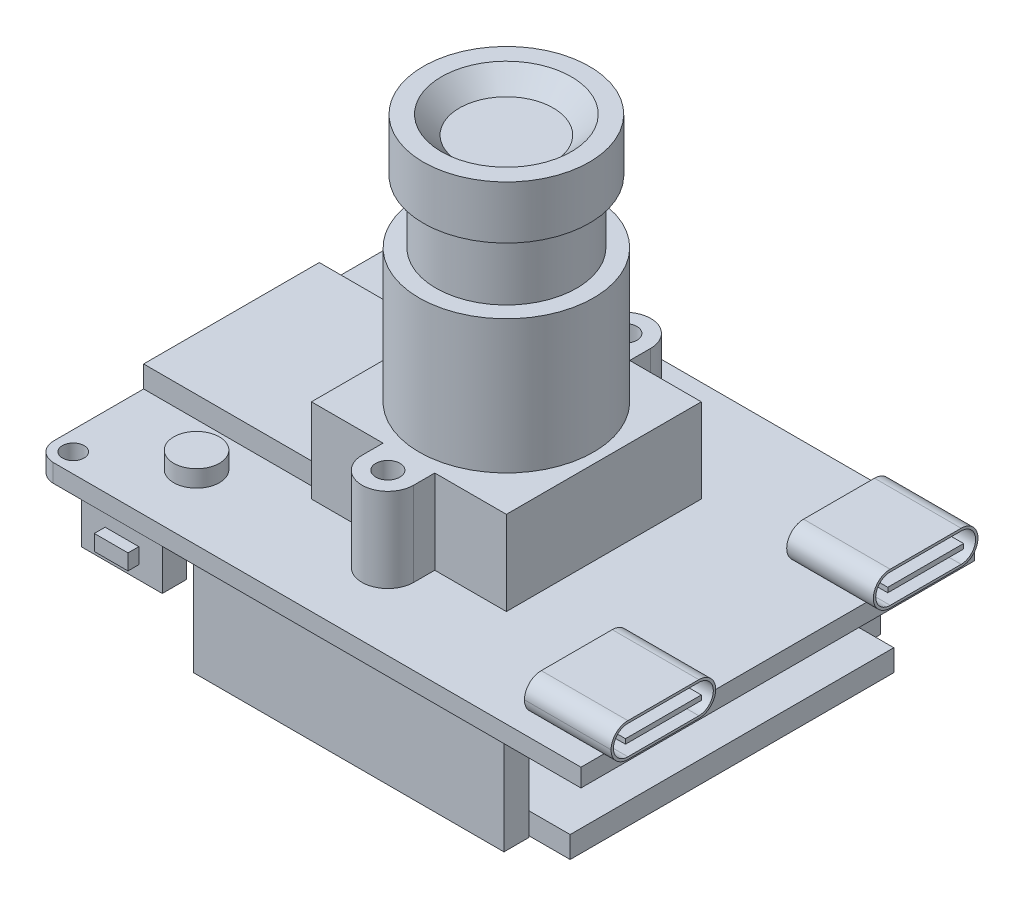
SolidWorks part; units mm, degrees
ref_plane "Alzado" through (0, 0, 0) normal (0, 0, 1) x (1, 0, 0)
ref_plane "Planta" through (0, 0, 0) normal (0, 1, 0) x (1, 0, 0)
ref_plane "Vista lateral" through (0, 0, 0) normal (1, 0, 0) x (0, 0, -1)
sketch "Croquis2" plane through (0, 0, 0) normal (0, 1, 0) x (1, 0, 0)
  line L1 (-16.6358, 13.4216) -> (28.7642, 13.4216)
  line L2 (-16.6358, 13.4216) -> (-16.6358, -19.2784)
  line L3 (-16.6358, -19.2784) -> (28.7642, -19.2784)
  line L4 (28.7642, 13.4216) -> (28.7642, -19.2784)
  dimension "D1" = 45.4
  dimension "D2" = 32.7
extrude "Saliente-Extruir1" add sketch "Croquis2" along normal blind 1.5
sketch "Croquis4" plane through (0, 1.5, 0) normal (0, 1, 0) x (1, 0, 0)
  line L0 (28.7642, -19.2784) -> (28.7642, 13.4216) construction
  line L1 (-1.7358, 5.0216) -> (4.2137, 5.0216)
  line L2 (-1.7358, 5.0216) -> (-1.7358, -11.1784)
  line L3 (-1.7358, -11.1784) -> (4.2137, -11.1784)
  line L4 (14.4642, 5.0216) -> (14.4642, -11.1784)
  line L5 (28.7642, 13.4216) -> (-16.6358, 13.4216) construction
  line L6 (6.3637, -12.9284) -> (6.3637, 6.7716) construction
  line L7 (6.3637, 6.7716) -> (6.3637, 8.9216) construction
  line L8 (-1.7358, -3.0784) -> (14.4642, -3.0784) construction
  line L9 (8.5137, 5.0216) -> (14.4642, 5.0216)
  line L11 (4.2137, 5.0216) -> (4.2137, 6.7716)
  line L13 (8.5137, 5.0216) -> (8.5137, 6.7716)
  line L14 (6.3637, -12.9284) -> (6.3637, -15.0784) construction
  line L15 (6.3637, 6.7716) -> (6.3637, -12.9284) construction
  line L16 (8.5137, -11.1784) -> (8.5137, -12.9284)
  line L17 (4.2137, -11.1784) -> (4.2137, -12.9284)
  line L18 (8.5137, -11.1784) -> (14.4642, -11.1784)
  line L19 (-1.7358, -11.1784) -> (4.2137, -11.1784)
  line L20 (8.5137, -11.1784) -> (14.4642, -11.1784)
  arc A0 (4.2137, 6.7716) -> (8.5137, 6.7716) centre (6.3637, 6.7716) cw
  arc A1 (4.2137, -12.9284) -> (8.5137, -12.9284) centre (6.3637, -12.9284) ccw
  circle A2 centre (6.3637, 6.7716) radius 1
  circle A3 centre (6.3637, -12.9284) radius 1
  point P18 (6.3637, 8.9216)
  dimension "D6" = 4.3
  dimension "D9" = 2
  dimension "D1" = 16.2
  dimension "D2" = 16.2
  dimension "D3" = 14.3
  dimension "D4" = 8.4
  dimension "D5" = 24
  dimension "D7" = 3.9
  dimension "D8" = 8.0995
extrude "Saliente-Extruir3" add sketch "Croquis4" along normal blind 7 contours L17 A1 L16 L18 L4 L9 L13 A0 L11 L1 L2 L3
sketch "Croquis5" plane through (0, 8.5, 0) normal (0, 1, 0) x (1, 0, 0)
  line L0 (-1.7358, -3.0784) -> (14.4642, -3.0784) construction
  line L1 (-1.7358, 5.0216) -> (-1.7358, -11.1784) construction
  line L2 (14.4642, 5.0216) -> (14.4642, -11.1784) construction
  circle A0 centre (6.3642, -3.0784) radius 7.25
  point P6 (6.3642, -3.0784)
  dimension "D1" = 14.5
extrude "Saliente-Extruir4" add sketch "Croquis5" along normal blind 11.1
sketch "Croquis7" plane through (0, 19.6, 0) normal (0, 1, 0) x (1, 0, 0)
  line L0 (-0.8858, -3.0784) -> (13.6142, -3.0784) construction
  circle A0 centre (6.3642, -3.0784) radius 7.25 construction
  circle A1 centre (6.3642, -3.0784) radius 7.25 construction
  circle A2 centre (6.3642, -3.0784) radius 5.85
  dimension "D1" = 11.7
extrude "Saliente-Extruir5" add sketch "Croquis7" along normal blind 5.2
sketch "Croquis13" plane through (0, 1.5, 0) normal (0, 1, 0) x (1, 0, 0)
  line L0 (28.7642, 13.4216) -> (-16.6358, 13.4216) construction
  line L1 (22.9642, 12.3216) -> (30.1642, 12.3216)
  line L2 (22.9642, 12.3216) -> (22.9642, 3.6216)
  line L3 (22.9642, 3.6216) -> (30.1642, 3.6216)
  line L4 (30.1642, 12.3216) -> (30.1642, 3.6216)
  line L5 (28.7642, -19.2784) -> (28.7642, 13.4216) construction
  line L6 (-16.6358, -2.9284) -> (28.7642, -2.9284) construction
  line L7 (-16.6358, 13.4216) -> (-16.6358, -19.2784) construction
  line L8 (30.1642, -18.1784) -> (30.1642, -9.4784)
  line L9 (22.9642, -9.4784) -> (30.1642, -9.4784)
  line L10 (22.9642, -18.1784) -> (22.9642, -9.4784)
  line L11 (22.9642, -18.1784) -> (30.1642, -18.1784)
  dimension "D1" = 8.7
  dimension "D2" = 7.2
  dimension "D3" = 1.1
  dimension "D4" = 1.4
extrude "Saliente-Extruir16" add sketch "Croquis13" along normal blind 2.8 contours L9 L8 L11 L10
sketch "Croquis20" plane through (30.1642, 0, 0) normal (1, 0, 0) x (0, 0, -1)
  line L0 (-16.7784, 2.9) -> (-10.8784, 2.9) construction
  line L1 (-16.7784, 4.3) -> (-10.8784, 4.3)
  line L2 (-16.7784, 1.5) -> (-10.8784, 1.5)
  line L3 (-18.1784, 1.5) -> (-9.4784, 1.5) construction
  line L4 (-9.4784, 4.3) -> (-9.4784, 1.5) construction
  line L5 (-18.1784, 4.3) -> (-18.1784, 1.5)
  line L6 (-18.1784, 1.5) -> (-16.7784, 1.5)
  line L7 (-10.8784, 4.3) -> (-9.4784, 4.3)
  line L8 (-9.4784, 4.3) -> (-9.4784, 1.5)
  line L9 (-9.4784, 1.5) -> (-10.8784, 1.5)
  arc A0 (-16.7784, 4.3) -> (-16.7784, 1.5) centre (-16.7784, 2.9) ccw
  arc A1 (-10.8784, 1.5) -> (-10.8784, 4.3) centre (-10.8784, 2.9) ccw
  arc A2 (-16.7784, 4.3) -> (-16.7502, 1.5) centre (-16.7782, 2.8999) ccw
  arc A3 (-10.8784, 4.3) -> (-10.8784, 1.5) centre (-10.8784, 2.9) cw
  spline S0 degree 1 poles (-16.7784, 4.3) (-18.1784, 4.3) knots 0 0 1 1
  point P2 (-13.8284, 2.9)
  point P7 (-18.1784, 2.9)
  point P8 (-9.4784, 2.9)
  line M5 (-18.1784, 1.5) -> (-9.4784, 1.5)
  line M6 (-9.4784, 1.5) -> (-9.4784, 4.3)
  line M7 (-9.4784, 4.3) -> (-18.1784, 4.3)
  line M8 (-18.1784, 4.3) -> (-18.1784, 1.5)
  dimension "D1" = 8.7
  dimension "D2" = 2.8
extrude "Cortar-Extruir2" cut sketch "Croquis20" against normal blind 7.2 contours A0 M7 M8 | A2 L5 M5 | A1 L8 M7 | A1 M5 M6
sketch "Croquis28" plane through (30.1642, 0, 0) normal (1, 0, 0) x (0, 0, -1)
  line L0 (-16.7784, 2.9) -> (-10.8784, 2.9) construction
  line L1 (-16.7784, 4.1) -> (-10.8784, 4.1)
  line L2 (-16.7784, 1.7) -> (-10.8784, 1.7)
  line L3 (-16.7784, 4.3) -> (-10.8784, 4.3) construction
  line L4 (-16.8063, 1.5) -> (-10.8784, 1.5) construction
  arc A0 (-16.7784, 4.1) -> (-16.7784, 1.7) centre (-16.7784, 2.9) ccw
  arc A1 (-10.8784, 1.7) -> (-10.8784, 4.1) centre (-10.8784, 2.9) ccw
  arc A2 (-10.8784, 1.5) -> (-10.8784, 4.3) centre (-10.8784, 2.9) ccw construction
  point P2 (-13.8284, 2.9)
  point P7 (-9.6784, 2.9)
  point P11 (-9.4784, 2.9)
  point P12 (-17.9784, 2.9)
  dimension "D1" = 0.2
  dimension "D2" = 0.2
  dimension "D3" = 0.2
  dimension "D4" = 0.2
sketch "Croquis29" plane through (30.1642, 0, 0) normal (1, 0, 0) x (0, 0, -1)
  line L0 (-16.7784, 4.1) -> (-10.8784, 4.1) construction
  line L1 (-16.9784, 3.1) -> (-10.6784, 3.1)
  line L2 (-16.9784, 3.1) -> (-16.9784, 2.7)
  line L3 (-16.9784, 2.7) -> (-10.6784, 2.7)
  line L4 (-10.6784, 3.1) -> (-10.6784, 2.7)
  line L5 (-16.7784, 1.7) -> (-10.8784, 1.7) construction
  arc A2 (-10.8784, 1.7) -> (-10.8784, 4.1) centre (-10.8784, 2.9) ccw construction
  arc A3 (-16.7784, 4.1) -> (-16.7784, 1.7) centre (-16.7784, 2.9) ccw construction
  point P15 (-9.6784, 2.9)
  point P16 (-17.9784, 2.9)
  dimension "D1" = 1
  dimension "D2" = 1
  dimension "D3" = 1
  dimension "D4" = 1
sketch "Croquis33" plane through (30.1642, 0, 0) normal (1, 0, 0) x (0, 0, -1)
  line L0 (-16.7784, 4.1) -> (-10.8784, 4.1)
  line L1 (-10.8784, 1.7) -> (-16.7784, 1.7)
  line L2 (-10.6784, 2.7) -> (-16.9784, 2.7)
  line L3 (-16.9784, 2.7) -> (-16.9784, 3.1)
  line L4 (-16.9784, 3.1) -> (-10.6784, 3.1)
  line L5 (-10.6784, 3.1) -> (-10.6784, 2.7)
  arc A0 (-16.7784, 4.1) -> (-16.7784, 1.7) centre (-16.7784, 2.9) ccw
  arc A1 (-10.8784, 4.1) -> (-10.8784, 1.7) centre (-10.8784, 2.9) cw
extrude "Cortar-Extruir3" cut sketch "Croquis33" against normal blind 7
sketch "Croquis34" plane through (0, 1.5, 0) normal (0, 1, 0) x (1, 0, 0)
  line L0 (-16.6358, -19.2784) -> (28.7642, -19.2784) construction
  line L1 (-16.6358, 4.3716) -> (-1.3358, 4.3716)
  line L2 (-16.6358, 4.3716) -> (-16.6358, -10.2284)
  line L3 (-16.6358, -10.2284) -> (-1.3358, -10.2284)
  line L4 (-1.3358, 4.3716) -> (-1.3358, -10.2284)
  line L5 (-16.6358, 13.4216) -> (-16.6358, -19.2784) construction
  dimension "D1" = 14.6
  dimension "D2" = 15.3
  dimension "D3" = 9.05
  dimension "D4" = 0
extrude "Saliente-Extruir17" add sketch "Croquis34" along normal blind 1.8
sketch "Croquis35" plane through (-16.6358, 0, 0) normal (-1, 0, 0) x (0, 0, 1)
  line L1 (-3.3716, 2.7) -> (7.8284, 2.7)
  line L2 (-3.3716, 2.7) -> (-3.3716, 1.5)
  line L3 (-3.3716, 1.5) -> (7.8284, 1.5)
  line L4 (7.8284, 2.7) -> (7.8284, 1.5)
  dimension "D1" = 1.2
  dimension "D2" = 11.2
  dimension "D3" = 1
  dimension "D4" = 0
extrude "Cortar-Extruir4" cut sketch "Croquis35" against normal blind 14
sketch "Croquis36" plane through (0, 1.5, 0) normal (0, 1, 0) x (1, 0, 0)
  line L1 (-16.6358, 13.4216) -> (-16.6358, 4.3716) construction
  line L2 (28.7642, 13.4216) -> (-16.6358, 13.4216) construction
  line L3 (-16.6358, -2.9284) -> (28.7642, -2.9284) construction
  line L4 (-16.6358, 4.3716) -> (-16.6358, -10.2284) construction
  line L5 (28.7642, -10.8784) -> (28.7642, 13.4216) construction
  circle A0 centre (-15.0358, 11.8216) radius 0.9
  circle A1 centre (-15.0358, -17.6784) radius 0.9
  dimension "D1" = 1.8
  dimension "D3" = 1.6
  dimension "D2" = 1.6
extrude "Cortar-Extruir5" cut sketch "Croquis36" against normal blind 14
sketch "Croquis41" plane through (0, 1.5, 0) normal (0, 1, 0) x (1, 0, 0)
  line L0 (-16.6358, 13.4216) -> (-16.6358, 4.3716) construction
  line L1 (28.7642, 13.4216) -> (-16.6358, 13.4216) construction
  line L2 (-16.6358, 11.7588) -> (-16.6358, 13.4216)
  line L3 (-16.6358, 13.4216) -> (-15.0986, 13.4216)
  line L4 (-16.6358, -2.9284) -> (28.7642, -2.9284) construction
  line L5 (-16.6358, 4.3716) -> (-16.6358, -10.2284) construction
  line L6 (28.7642, -10.8784) -> (28.7642, 13.4216) construction
  line L7 (-16.6358, -19.2784) -> (-15.0986, -19.2784)
  line L8 (-16.6358, -17.6156) -> (-16.6358, -19.2784)
  arc A0 (-16.6358, 11.7588) -> (-15.0986, 13.4216) centre (-15.0358, 11.8216) cw
  circle A1 centre (-15.0358, 11.8216) radius 0.9 construction
  arc A2 (-16.6358, -17.6156) -> (-15.0986, -19.2784) centre (-15.0358, -17.6784) ccw
  line M7 (-16.6358, -19.2784) -> (28.7642, -19.2784)
  line M13 (28.7642, 13.4216) -> (-16.6358, 13.4216)
  line M14 (-16.6358, 13.4216) -> (-16.6358, 4.3716)
  dimension "D1" = 1.5372
extrude "Cortar-Extruir6" cut sketch "Croquis41" against normal blind 14 contours A0 M14 M13 | A2 L8 M7
sketch "Croquis42" plane through (0, 1.5, 0) normal (0, 1, 0) x (1, 0, 0)
  line L0 (-16.6358, -10.2284) -> (-16.6358, -17.7412) construction
  line L1 (-16.6358, -10.2284) -> (-1.7358, -10.2284) construction
  circle A0 centre (-8.6358, -13.8284) radius 1.9
  dimension "D1" = 3.8
  dimension "D3" = 3.6
  dimension "D2" = 8
extrude "Saliente-Extruir18" add sketch "Croquis42" along normal blind 1.4
sketch "Croquis43" plane through (0, 0, 0) normal (0, -1, 0) x (1, 0, 0)
  line L0 (-16.6358, 2.9284) -> (28.7642, 2.9284) construction
  line L1 (-16.6358, -11.8844) -> (-16.6358, 17.7412) construction
  line L2 (28.7642, 19.2784) -> (28.7642, -13.4216) construction
  line L4 (-4.1358, 18.5784) -> (21.6642, 18.5784)
  line L5 (-4.1358, 18.5784) -> (-4.1358, 16.4784)
  line L6 (-4.1358, 16.4784) -> (21.6642, 16.4784)
  line L7 (21.6642, 18.5784) -> (21.6642, 16.4784)
  line L8 (-15.0986, 19.2784) -> (28.7642, 19.2784) construction
  line L9 (21.6642, -12.7216) -> (21.6642, -10.6216)
  line L10 (-4.1358, -10.6216) -> (21.6642, -10.6216)
  line L11 (-4.1358, -12.7216) -> (-4.1358, -10.6216)
  line L12 (-4.1358, -12.7216) -> (21.6642, -12.7216)
  dimension "D1" = 25.8
  dimension "D2" = 2.1
  dimension "D3" = 7.1
  dimension "D4" = 0.7
extrude "Saliente-Extruir19" add sketch "Croquis43" along normal blind 8.5
sketch "Croquis44" plane through (0, -8.5, 0) normal (0, -1, 0) x (1, 0, 0)
  line L0 (-0.6849, 18.0784) -> (0.4151, 18.0784)
  line L1 (-3.2358, 18.0784) -> (-2.1358, 18.0784)
  line L2 (-3.2358, 18.0784) -> (-3.2358, 16.9784)
  line L3 (-3.2358, 16.9784) -> (-2.1358, 16.9784)
  line L4 (-2.1358, 18.0784) -> (-2.1358, 16.9784)
  line L8 (-4.1358, 17.5284) -> (21.6642, 17.5284) construction
  line L9 (-4.1358, 18.5784) -> (-4.1358, 16.4784) construction
  line L10 (21.6642, 16.4784) -> (21.6642, 18.5784) construction
  line L11 (-0.6849, 18.0784) -> (-0.6849, 16.9784)
  line L12 (-0.6849, 16.9784) -> (0.4151, 16.9784)
  line L13 (0.4151, 18.0784) -> (0.4151, 16.9784)
  line L14 (1.8659, 18.0784) -> (2.9659, 18.0784)
  line L15 (1.8659, 18.0784) -> (1.8659, 16.9784)
  line L16 (1.8659, 16.9784) -> (2.9659, 16.9784)
  line L17 (2.9659, 18.0784) -> (2.9659, 16.9784)
  line L18 (4.4167, 18.0784) -> (5.5167, 18.0784)
  line L19 (4.4167, 18.0784) -> (4.4167, 16.9784)
  line L20 (4.4167, 16.9784) -> (5.5167, 16.9784)
  line L21 (5.5167, 18.0784) -> (5.5167, 16.9784)
  line L22 (6.9676, 18.0784) -> (8.0676, 18.0784)
  line L23 (6.9676, 18.0784) -> (6.9676, 16.9784)
  line L24 (6.9676, 16.9784) -> (8.0676, 16.9784)
  line L25 (8.0676, 18.0784) -> (8.0676, 16.9784)
  line L26 (9.5184, 18.0784) -> (10.6184, 18.0784)
  line L27 (9.5184, 18.0784) -> (9.5184, 16.9784)
  line L28 (9.5184, 16.9784) -> (10.6184, 16.9784)
  line L29 (10.6184, 18.0784) -> (10.6184, 16.9784)
  line L30 (12.0693, 18.0784) -> (13.1693, 18.0784)
  line L31 (12.0693, 18.0784) -> (12.0693, 16.9784)
  line L32 (12.0693, 16.9784) -> (13.1693, 16.9784)
  line L33 (13.1693, 18.0784) -> (13.1693, 16.9784)
  line L34 (14.6201, 18.0784) -> (15.7201, 18.0784)
  line L35 (14.6201, 18.0784) -> (14.6201, 16.9784)
  line L36 (14.6201, 16.9784) -> (15.7201, 16.9784)
  line L37 (15.7201, 18.0784) -> (15.7201, 16.9784)
  line L38 (17.1709, 18.0784) -> (18.2709, 18.0784)
  line L39 (17.1709, 18.0784) -> (17.1709, 16.9784)
  line L40 (17.1709, 16.9784) -> (18.2709, 16.9784)
  line L41 (18.2709, 18.0784) -> (18.2709, 16.9784)
  line L42 (19.7218, 18.0784) -> (20.8218, 18.0784)
  line L43 (19.7218, 18.0784) -> (19.7218, 16.9784)
  line L44 (19.7218, 16.9784) -> (20.8218, 16.9784)
  line L45 (20.8218, 18.0784) -> (20.8218, 16.9784)
  line L46 (19.7218, 18.0784) -> (20.8218, 18.0784)
  line L47 (19.7218, 16.9784) -> (20.8218, 16.9784)
  line L48 (17.1709, 18.0784) -> (18.2709, 18.0784)
  line L49 (17.1709, 16.9784) -> (18.2709, 16.9784)
  line L50 (14.6201, 18.0784) -> (15.7201, 18.0784)
  line L51 (14.6201, 16.9784) -> (15.7201, 16.9784)
  line L52 (12.0693, 18.0784) -> (13.1693, 18.0784)
  line L53 (12.0693, 16.9784) -> (13.1693, 16.9784)
  line L54 (9.5184, 18.0784) -> (10.6184, 18.0784)
  line L55 (9.5184, 16.9784) -> (10.6184, 16.9784)
  line L56 (6.9676, 18.0784) -> (8.0676, 18.0784)
  line L57 (6.9676, 16.9784) -> (8.0676, 16.9784)
  line L58 (4.4167, 18.0784) -> (5.5167, 18.0784)
  line L59 (4.4167, 16.9784) -> (5.5167, 16.9784)
  line L60 (1.8659, 18.0784) -> (2.9659, 18.0784)
  line L61 (1.8659, 16.9784) -> (2.9659, 16.9784)
  line L62 (-0.6849, 18.0784) -> (0.4151, 18.0784)
  line L63 (-3.2358, 18.0784) -> (-2.1358, 18.0784)
  line L64 (-3.2358, 16.9784) -> (-2.1358, 16.9784)
  line L65 (-0.6849, 16.9784) -> (0.4151, 16.9784)
  point P16 (-3.2358, 17.5284)
  point P23 (-0.6849, 17.5284)
  point P28 (1.8659, 17.5284)
  point P33 (4.4167, 17.5284)
  point P38 (6.9676, 17.5284)
  point P43 (9.5184, 17.5284)
  point P48 (12.0693, 17.5284)
  point P53 (14.6201, 17.5284)
  point P58 (17.1709, 17.5284)
  point P63 (19.7218, 17.5284)
  dimension "D1" = 1.1
  dimension "D2" = 1.1
  dimension "D3" = 0.9
  dimension "D4" = 10
extrude "Cortar-Extruir9" cut sketch "Croquis44" against normal blind 8.5 contours L2 L8 L4 L1 | L8 L2 L3 L4 | L11 L8 L13 L0 | L8 L11 L12 L13 | L8 L15 L16 L17 | L15 L8 L17 L14 | L8 L19 L20 L21 | L19 L8 L21 L18 | L8 L23 L24 L25 | L23 L8 L25 L22 | L27 L8 L29 L26 | L8 L27 L28 L29 | L31 L8 L33 L30 | L8 L31 L32 L33 | L35 L8 L37 L34 | L8 L35 L36 L37 | L39 L8 L41 L38 | L8 L39 L40 L41 | L43 L8 L45 L42 | L8 L43 L44 L45
sketch "Croquis45" plane through (0, 0, 0) normal (0, -1, 0) x (1, 0, 0)
  line L0 (-16.6358, -11.8844) -> (-16.6358, 17.7412) construction
  line L1 (-12.8358, 19.1784) -> (-6.1358, 19.1784)
  line L2 (-12.8358, 19.1784) -> (-12.8358, 17.1784)
  line L3 (-12.8358, 17.1784) -> (-6.1358, 17.1784)
  line L4 (-6.1358, 19.1784) -> (-6.1358, 17.1784)
  line L5 (-15.0986, 19.2784) -> (28.7642, 19.2784) construction
  line L6 (-16.6358, 2.9284) -> (28.7642, 2.9284) construction
  line L7 (28.7642, 19.2784) -> (28.7642, -13.4216) construction
  line L8 (-6.1358, -13.3216) -> (-6.1358, -11.3216)
  line L9 (-12.8358, -11.3216) -> (-6.1358, -11.3216)
  line L10 (-12.8358, -13.3216) -> (-12.8358, -11.3216)
  line L11 (-12.8358, -13.3216) -> (-6.1358, -13.3216)
  dimension "D1" = 6.7
  dimension "D2" = 2
  dimension "D3" = 3.8
  dimension "D4" = 0.1
extrude "Saliente-Extruir20" add sketch "Croquis45" along normal blind 3.5
sketch "Croquis49" plane through (0, 0, 0) normal (0, -1, 0) x (1, 0, 0)
  line L1 (-16.5358, -2.2216) -> (-14.5358, -2.2216)
  line L2 (-16.5358, -2.2216) -> (-16.5358, -8.9216)
  line L3 (-16.5358, -8.9216) -> (-14.5358, -8.9216)
  line L4 (-14.5358, -2.2216) -> (-14.5358, -8.9216)
  line L8 (-16.6358, -11.8844) -> (-16.6358, 17.7412) construction
  line L9 (28.7642, -13.4216) -> (-15.0986, -13.4216) construction
  dimension "D1" = 6.7
  dimension "D2" = 2
  dimension "D3" = 0.1
  dimension "D4" = 4.5
extrude "Saliente-Extruir23" add sketch "Croquis49" along normal blind 3.4
sketch "Croquis50" plane through (-16.5358, 0, 0) normal (-1, 0, 0) x (0, 0, 1)
  line L1 (-6.9716, -1.1) -> (-4.1716, -1.1)
  line L2 (-6.9716, -1.1) -> (-6.9716, -2.4)
  line L3 (-6.9716, -2.4) -> (-4.1716, -2.4)
  line L4 (-4.1716, -1.1) -> (-4.1716, -2.4)
  dimension "D1" = 2.8
  dimension "D2" = 1.3
  dimension "D3" = 1.1
  dimension "D4" = 1.95
  dimension "D5" = 1.95
extrude "Saliente-Extruir24" add sketch "Croquis50" along normal blind 1.1
sketch "Croquis51" plane through (0, -8.5, 0) normal (0, -1, 0) x (1, 0, 0)
  line L1 (-4.1358, 16.3784) -> (24.9642, 16.3784)
  line L2 (-4.1358, 16.3784) -> (-4.1358, -10.5216)
  line L3 (-4.1358, -10.5216) -> (24.9642, -10.5216)
  line L4 (24.9642, 16.3784) -> (24.9642, -10.5216)
  line L5 (-4.1358, 18.5784) -> (-4.1358, 16.4784) construction
  line L7 (-4.1358, 16.4784) -> (21.6642, 16.4784) construction
  dimension "D1" = 29.1
  dimension "D2" = 0.1
  dimension "D3" = 0.1
  dimension "D4" = 0
extrude "Saliente-Extruir26" add sketch "Croquis51" against normal blind 1.8 separate body
sketch "Croquis52" plane through (0, 0, 0) normal (0, -1, 0) x (1, 0, 0)
  line L0 (-16.6358, -11.8844) -> (-16.6358, 17.7412) construction
  line L1 (-16.5358, 13.7784) -> (-12.3358, 13.7784)
  line L2 (-16.5358, 13.7784) -> (-16.5358, 6.4784)
  line L3 (-16.5358, 6.4784) -> (-12.3358, 6.4784)
  line L4 (-12.3358, 13.7784) -> (-12.3358, 6.4784)
  line L5 (-15.0986, 19.2784) -> (28.7642, 19.2784) construction
  dimension "D1" = 7.3
  dimension "D2" = 4.2
  dimension "D3" = 0.1
  dimension "D4" = 5.5
extrude "Saliente-Extruir27" add sketch "Croquis52" along normal blind 3.7
sketch "Croquis54" plane through (-16.5358, 0, 0) normal (-1, 0, 0) x (0, 0, 1)
  line L6 (10.1284, -3.7) -> (10.1284, -0.6251) construction
  line L7 (13.7784, -3.7) -> (6.4784, -3.7) construction
  line L8 (12.7784, 0) -> (12.7784, -2.7)
  line L9 (6.4784, 0) -> (7.4784, 0)
  line L10 (6.4784, 0) -> (6.4784, -2.7)
  line L11 (6.4784, -2.7) -> (7.4784, -2.7)
  line L12 (7.4784, 0) -> (7.4784, -2.7)
  line L13 (13.7784, -2.7) -> (12.7784, -2.7)
  line L14 (13.7784, 0) -> (13.7784, -2.7)
  line L15 (13.7784, 0) -> (12.7784, 0)
  dimension "D1" = 1
  dimension "D2" = 1
extrude "Cortar-Extruir10" cut sketch "Croquis54" against normal blind 1
sketch "Croquis57" plane through (-16.5358, 0, 0) normal (-1, 0, 0) x (0, 0, 1)
  line L0 (13.7784, -3.7) -> (6.4784, -3.7) construction
  line L1 (6.4784, -2.7) -> (7.4784, -2.7)
  line L2 (6.4784, -2.7) -> (6.4784, -3.7)
  line L3 (6.4784, -3.7) -> (7.4784, -3.7)
  line L4 (7.4784, -2.7) -> (7.4784, -3.7)
  line L6 (12.7784, -2.7) -> (13.7784, -2.7)
  line L7 (12.7784, -2.7) -> (12.7784, -3.7)
  line L8 (12.7784, -3.7) -> (13.7784, -3.7)
  line L9 (13.7784, -2.7) -> (13.7784, -3.7)
extrude "Cortar-Extruir11" cut sketch "Croquis57" against normal blind 7
sketch "Croquis58" plane through (-16.5358, 0, 0) normal (-1, 0, 0) x (0, 0, 1)
  line L0 (12.7784, 0) -> (7.4784, 0) construction
  line L1 (7.5784, -0.1) -> (12.6784, -0.1)
  line L2 (7.5784, -0.1) -> (7.5784, -3.6)
  line L3 (7.5784, -3.6) -> (12.6784, -3.6)
  line L4 (12.6784, -0.1) -> (12.6784, -3.6)
  line L5 (12.7784, -3.7) -> (7.4784, -3.7) construction
  line L6 (12.7784, 0) -> (12.7784, -3.7) construction
  line L7 (7.4784, -3.7) -> (7.4784, 0) construction
  dimension "D1" = 0.1
  dimension "D2" = 0.1
  dimension "D3" = 0.1
  dimension "D4" = 0.1
extrude "Cortar-Extruir12" cut sketch "Croquis58" against normal blind 4
sketch "Croquis60" plane through (-12.5358, 0, 0) normal (-1, 0, 0) x (0, 0, 1)
  line L0 (10.1284, -3.6) -> (10.1284, -0.1) construction
  line L1 (7.5784, -3.6) -> (12.6784, -3.6) construction
  line L2 (12.6784, -0.1) -> (7.5784, -0.1) construction
  line L3 (11.0302, -1.9634) -> (10.6342, -1.9634)
  line L4 (9.2266, -1.5728) -> (9.6225, -1.5728)
  line L5 (9.2266, -1.5728) -> (9.2266, -1.9634)
  line L6 (9.2266, -1.9634) -> (9.6225, -1.9634)
  line L7 (9.6225, -1.5728) -> (9.6225, -1.9634)
  line L8 (10.6342, -1.5728) -> (10.6342, -1.9634)
  line L9 (11.0302, -1.5728) -> (11.0302, -1.9634)
  line L10 (11.0302, -1.5728) -> (10.6342, -1.5728)
  line L11 (7.5784, -3.6) -> (12.6784, -3.6) construction
  line L12 (7.5784, -0.1) -> (7.5784, -3.6) construction
  dimension "D1" = 1.4728
  dimension "D2" = 1.6366
  dimension "D3" = 0.3905
  dimension "D4" = 0.396
  dimension "D5" = 1.6482
sketch "Croquis61" plane through (-12.5358, 0, 0) normal (-1, 0, 0) x (0, 0, 1)
extrude "Saliente-Extruir29" add sketch "Croquis60" along normal blind 4
ref_plane "Plano1" through (0, 0, 2.9284) normal (0, 0, 1) x (1, 0, 0)
mirror "Simetría1" about plane through (0, 0, 2.9284) normal (0, 0, 1) of "Cortar-Extruir3", "Cortar-Extruir2", "Saliente-Extruir16"
mirror "Simetría13" about plane through (0, 0, 2.9284) normal (0, 0, 1) of "Cortar-Extruir9"
sketch "Croquis63" plane through (0, 0, 19.1784) normal (0, 0, 1) x (1, 0, 0)
  line L0 (-12.8358, -3.5) -> (-12.8358, 0) construction
  line L1 (-10.8858, -1.1) -> (-8.0858, -1.1)
  line L2 (-10.8858, -1.1) -> (-10.8858, -2.4)
  line L3 (-10.8858, -2.4) -> (-8.0858, -2.4)
  line L4 (-8.0858, -1.1) -> (-8.0858, -2.4)
  dimension "D1" = 2.8
  dimension "D2" = 1.3
  dimension "D3" = 1.95
extrude "Saliente-Extruir30" add sketch "Croquis63" along normal blind 0.9
sketch "Croquis64" plane through (0, 0, -13.3216) normal (0, 0, -1) x (-1, 0, 0)
  line L0 (12.8358, -3.5) -> (6.1358, -3.5) construction
  line L1 (8.0858, -1.1) -> (10.8858, -1.1)
  line L2 (8.0858, -1.1) -> (8.0858, -2.4)
  line L3 (8.0858, -2.4) -> (10.8858, -2.4)
  line L4 (10.8858, -1.1) -> (10.8858, -2.4)
  line L5 (12.8358, -3.5) -> (12.8358, 0) construction
  dimension "D1" = 2.8
  dimension "D2" = 1.3
  dimension "D3" = 1.1
  dimension "D4" = 1.95
extrude "Saliente-Extruir31" add sketch "Croquis64" along normal blind 0.9
sketch "Croquis66" plane through (0, 24.8, 0) normal (0, 1, 0) x (1, 0, 0)
  line L0 (6.3642, 2.7716) -> (6.3642, -8.9284) construction
  circle A0 centre (6.3642, -3.0784) radius 5.85 construction
  circle A1 centre (6.3642, -3.0784) radius 6.9
  dimension "D1" = 13.8
extrude "Saliente-Extruir32" add sketch "Croquis66" along normal blind 4.4
sketch "Croquis67" plane through (0, 29.2, 0) normal (0, 1, 0) x (1, 0, 0)
  line L0 (6.3642, 3.8216) -> (6.3642, -9.9784) construction
  circle A0 centre (6.3642, -3.0784) radius 6.9 construction
  circle A1 centre (6.3642, -3.0784) radius 5.9
  dimension "D1" = 1
extrude "Cortar-Extruir13" cut sketch "Croquis67" against normal blind 1.5
chamfer "Chaflán1" distance 2 angle 45 1 edges at (6.3642, 27.7, 8.9784)
